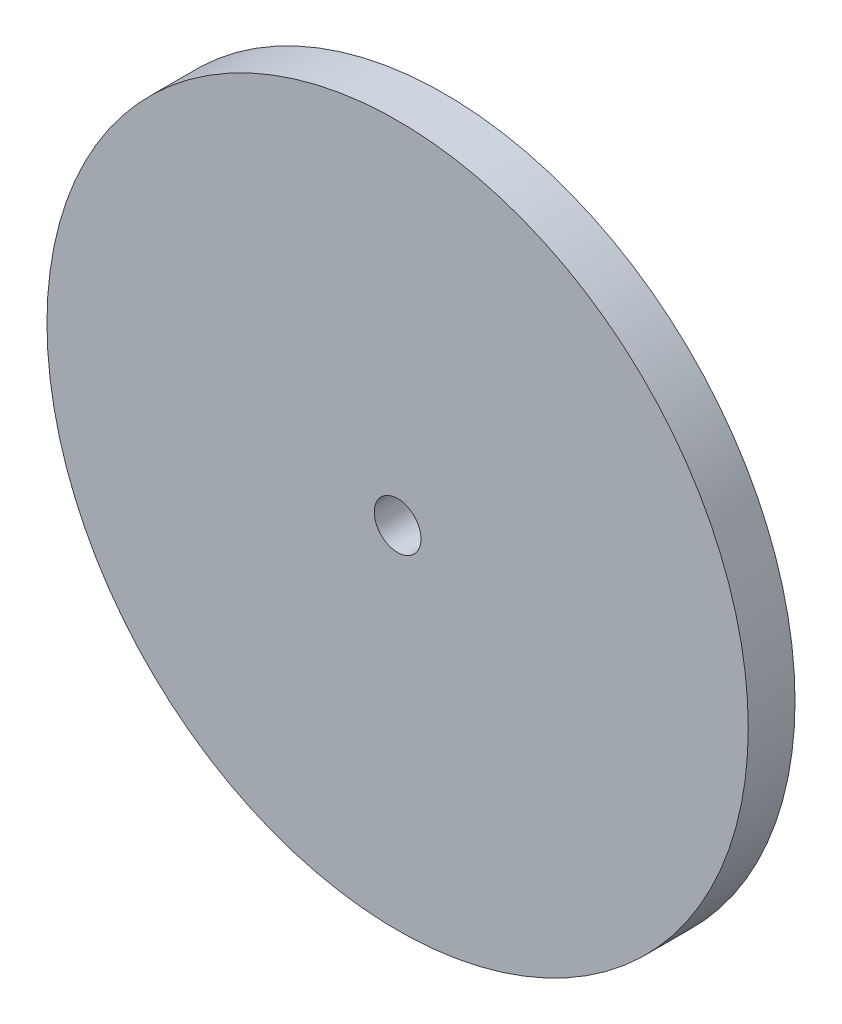
SolidWorks part; units mm, degrees
ref_plane "Front Plane" through (0, 0, 0) normal (0, 0, 1) x (1, 0, 0)
ref_plane "Top Plane" through (0, 0, 0) normal (0, 1, 0) x (1, 0, 0)
ref_plane "Right Plane" through (0, 0, 0) normal (1, 0, 0) x (0, 0, -1)
sketch "Sketch1" plane through (0, 0, 0) normal (0, 0, 1) x (1, 0, 0)
  circle A0 centre (0, 0) radius 15
extrude "Boss-Extrude1" add sketch "Sketch1" along normal blind 2
sketch "Sketch2" plane through (0, 0, 2) normal (0, 0, 1) x (1, 0, 0)
  circle A0 centre (0, 0) radius 1
extrude "Cut-Extrude1" cut sketch "Sketch2" against normal blind 2
